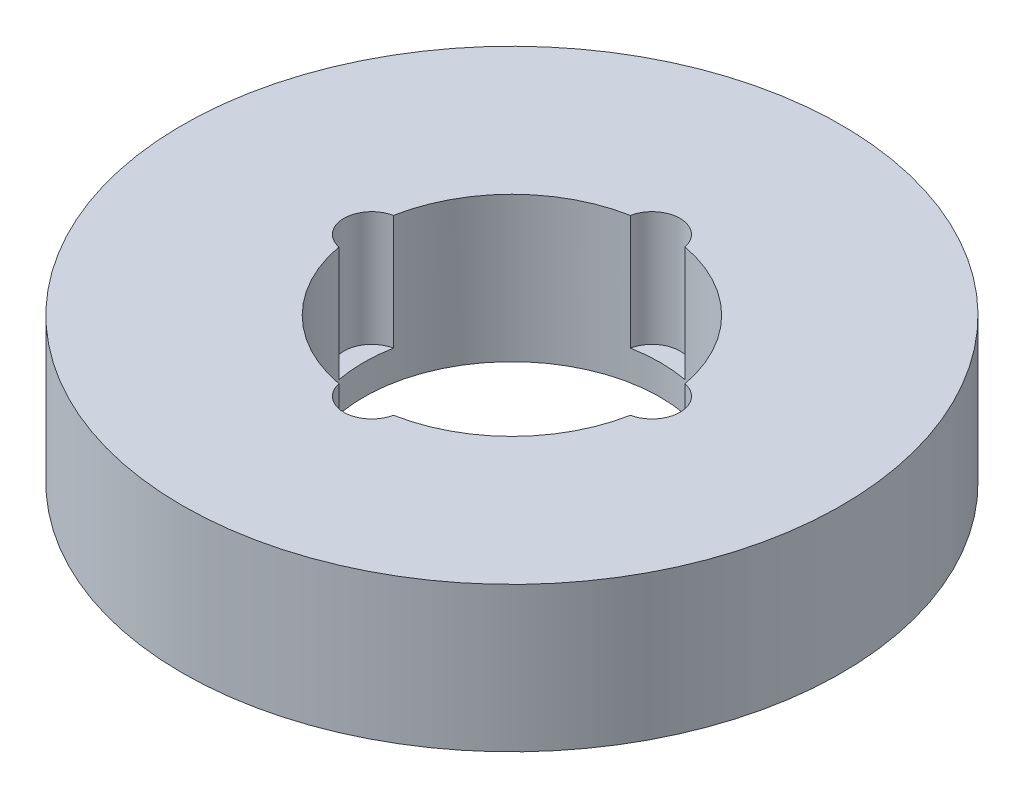
SolidWorks part; units mm, degrees
ref_plane "Front Plane" through (0, 0, 0) normal (0, 0, 1) x (1, 0, 0)
ref_plane "Top Plane" through (0, 0, 0) normal (0, 1, 0) x (1, 0, 0)
ref_plane "Right Plane" through (0, 0, 0) normal (1, 0, 0) x (0, 0, -1)
sketch "Sketch1" plane through (0, 0, 0) normal (0, 1, 0) x (1, 0, 0)
  circle A0 centre (0, 0) radius 50
  dimension "FLANGE_OD" = 100
extrude "Boss-Extrude1" add sketch "Sketch1" along normal blind 22
sketch "Sketch2" plane through (0, 0, 0) normal (0, 1, 0) x (1, 0, 0)
  circle A0 centre (0, 0) radius 22.5
  dimension "BORE_D" = 45
extrude "Cut-Extrude1" cut sketch "Sketch2" along normal through all
sketch "Sketch3" plane through (0, 22, 0) normal (0, 1, 0) x (1, 0, 0)
  circle A0 centre (0, 0) radius 21.2633 construction
  circle A1 centre (-21.2633, 0) radius 4.2291
  dimension "BOLT_D" = 8.4581
  dimension "BOLT_PCD" = 42.5265
extrude "Cut-Extrude2" cut sketch "Sketch3" against normal blind 17.4381
pattern_circular "CirPattern1" count 4 over 360 about axis through (0, 0, 0) along (0, 1, 0) of "Cut-Extrude2"
